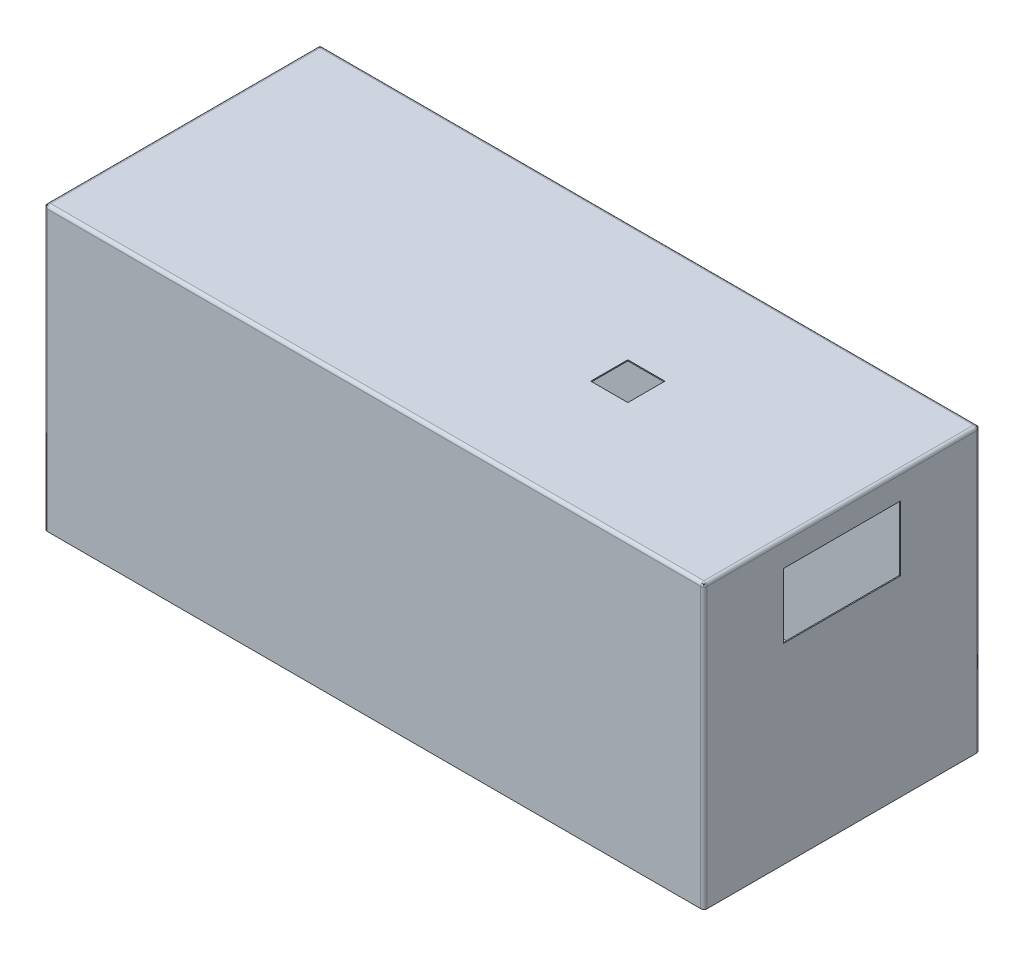
SolidWorks part; units mm, degrees
material "Alumina"
ref_plane "Front Plane" through (0, 0, 0) normal (0, 0, 1) x (1, 0, 0)
ref_plane "Top Plane" through (0, 0, 0) normal (0, 1, 0) x (1, 0, 0)
ref_plane "Right Plane" through (0, 0, 0) normal (1, 0, 0) x (0, 0, -1)
sketch "Sketch2" plane through (0, 0, 0) normal (0, 1, 0) x (1, 0, 0)
  line L1 (-508.1, 212.5) -> (508.1, 212.5)
  line L2 (-508.1, 212.5) -> (-508.1, -212.5)
  line L3 (-508.1, -212.5) -> (508.1, -212.5)
  line L4 (508.1, 212.5) -> (508.1, -212.5)
  line L5 (-508.1, 212.5) -> (508.1, -212.5) construction
  line L6 (-508.1, -212.5) -> (508.1, 212.5) construction
  line L7 (-506.5125, 210.9125) -> (506.5125, 210.9125)
  line L8 (-506.5125, 210.9125) -> (-506.5125, -210.9125)
  line L9 (-506.5125, -210.9125) -> (506.5125, -210.9125)
  line L10 (506.5125, 210.9125) -> (506.5125, -210.9125)
  line L11 (-506.5125, 210.9125) -> (506.5125, -210.9125) construction
  line L12 (-506.5125, -210.9125) -> (506.5125, 210.9125) construction
  point P0 (0, 0)
  point P6 (0, 0)
  dimension "D1" = 1016.2
  dimension "D2" = 425
  dimension "D3" = 1013.025
  dimension "D4" = 421.825
extrude "Boss-Extrude1" add sketch "Sketch2" along normal blind 435
sketch "Sketch3" plane through (0, 0, 0) normal (0, 1, 0) x (1, 0, 0)
  line L1 (-508.1, 212.5) -> (508.1, 212.5)
  line L2 (-508.1, 212.5) -> (-508.1, -212.5)
  line L3 (-508.1, -212.5) -> (508.1, -212.5)
  line L4 (508.1, 212.5) -> (508.1, -212.5)
  line L5 (-508.1, 212.5) -> (508.1, -212.5) construction
  line L6 (-508.1, -212.5) -> (508.1, 212.5) construction
  point P0 (0, 0)
  dimension "D1" = 1016.2
  dimension "D2" = 425
extrude "Boss-Extrude2" add sketch "Sketch3" against normal blind 1.5875 from offset 435
fillet "Fillet2" radius 5 8 edges at (0, 435, 212.5) (-508.1, 435, 0) (0, 435, -212.5) (508.1, 435, 0) (508.1, 217.5, 212.5) (-508.1, 217.5, 212.5) (-508.1, 217.5, -212.5) (508.1, 217.5, -212.5)
sketch "Sketch4" plane through (-508.1, 0, 0) normal (-1, 0, 0) x (0, 0, 1)
  line L0 (-207.5, 0) -> (207.5, 0) construction
  line L1 (-40, 0) -> (40, 0)
  line L2 (-40, 0) -> (-40, 80)
  line L3 (-40, 80) -> (40, 80)
  line L4 (40, 0) -> (40, 80)
  line L5 (-40, 0) -> (40, 80) construction
  line L6 (-40, 80) -> (40, 0) construction
  point P4 (0, 40)
  dimension "D1" = 80
  dimension "D2" = 80
extrude "Cut-Extrude1" cut sketch "Sketch4" against normal up to next
sketch "Sketch5" plane through (0, 0, 212.5) normal (0, 0, 1) x (1, 0, 0)
  line L0 (102.4542, 1871.2645) -> (102.4542, 2121.2645) construction
  dimension "D1" = 250
sketch "Sketch6" plane through (0, 0, -212.5) normal (0, 0, -1) x (-1, 0, 0)
  line L0 (-163.7052, 31.2035) -> (-163.7052, 281.2035) construction
  dimension "D1" = 250
sketch "Sketch7" plane through (0, 0, 0) normal (0, 1, 0) x (1, 0, 0)
  line L0 (-239.25, 0) -> (239.25, 0) construction
  line L1 (149.825, 28.575) -> (206.975, 28.575)
  line L2 (149.825, 28.575) -> (149.825, -28.575)
  line L3 (149.825, -28.575) -> (206.975, -28.575)
  line L4 (206.975, 28.575) -> (206.975, -28.575)
  line L5 (149.825, 28.575) -> (206.975, -28.575) construction
  line L6 (149.825, -28.575) -> (206.975, 28.575) construction
  point P0 (178.4, 0)
  point P8 (0, 0)
  dimension "D1" = 57.15
  dimension "D2" = 178.4
extrude "Cut-Extrude2" cut sketch "Sketch7" along normal up to surface (435 mm away) up to face at (0, 435, 0)
sketch "Sketch8" plane through (0, 0, 0) normal (1, 0, 0) x (0, 0, -1)
  line L0 (0, 264) -> (0, -264) construction
  line L1 (-90, 395) -> (90, 395)
  line L2 (-90, 395) -> (-90, 295)
  line L3 (-90, 295) -> (90, 295)
  line L4 (90, 395) -> (90, 295)
  line L5 (-90, 395) -> (90, 295) construction
  line L6 (-90, 295) -> (90, 395) construction
  line L7 (233.75, 0) -> (-233.75, 0) construction
  point P0 (0, 345)
  dimension "D1" = 345
  dimension "D2" = 180
  dimension "D3" = 100
extrude "Cut-Extrude3" cut sketch "Sketch8" along normal up to surface (508.1 mm away) up to face at (508.1, 215, 0)
sketch "Sketch9" plane through (0, 0, 0) normal (1, 0, 0) x (0, 0, -1)
  line L0 (0, 231) -> (0, -231) construction
  line L1 (90, 180) -> (-90, 180)
  line L2 (90, 180) -> (90, 80)
  line L3 (90, 80) -> (-90, 80)
  line L4 (-90, 180) -> (-90, 80)
  line L5 (90, 180) -> (-90, 80) construction
  line L6 (90, 80) -> (-90, 180) construction
  line L7 (233.75, 0) -> (-233.75, 0) construction
  point P0 (0, 130)
  dimension "D1" = 180
  dimension "D2" = 100
  dimension "D3" = 130
extrude "Cut-Extrude4" cut sketch "Sketch9" against normal up to surface (508.1 mm away) up to face at (-508.1, 127.5, 0)
equation "\"sheetMetalThickness\"= 1in / 16"
equation "\"shellLength\"= 920mm + 3in + 20mm"
equation "\"shellWidth\"= 425mm"
equation "\"shellHeight\"= 435mm"
equation "\"D1@Sketch2\"=\"shellLength\""
equation "\"D2@Sketch2\"=\"shellWidth\""
equation "\"D3@Sketch2\"=\"shellLength\"-\"sheetMetalThickness\"*2"
equation "\"D4@Sketch2\"=\"shellWidth\"-\"sheetMetalThickness\"*2"
equation "\"D1@Boss-Extrude1\"=\"shellHeight\""
equation "\"D1@Sketch3\"=\"shellLength\""
equation "\"D2@Sketch3\"=\"shellWidth\""
equation "\"D19@Boss-Extrude2\"=\"shellHeight\""
equation "\"D1@Boss-Extrude2\"=\"sheetMetalThickness\""
equation "\"D2@Sketch7\"=\"shellLength\"/2 -329.7"
equation "\"D1@Sketch8\"=\"shellHeight\"-90"
